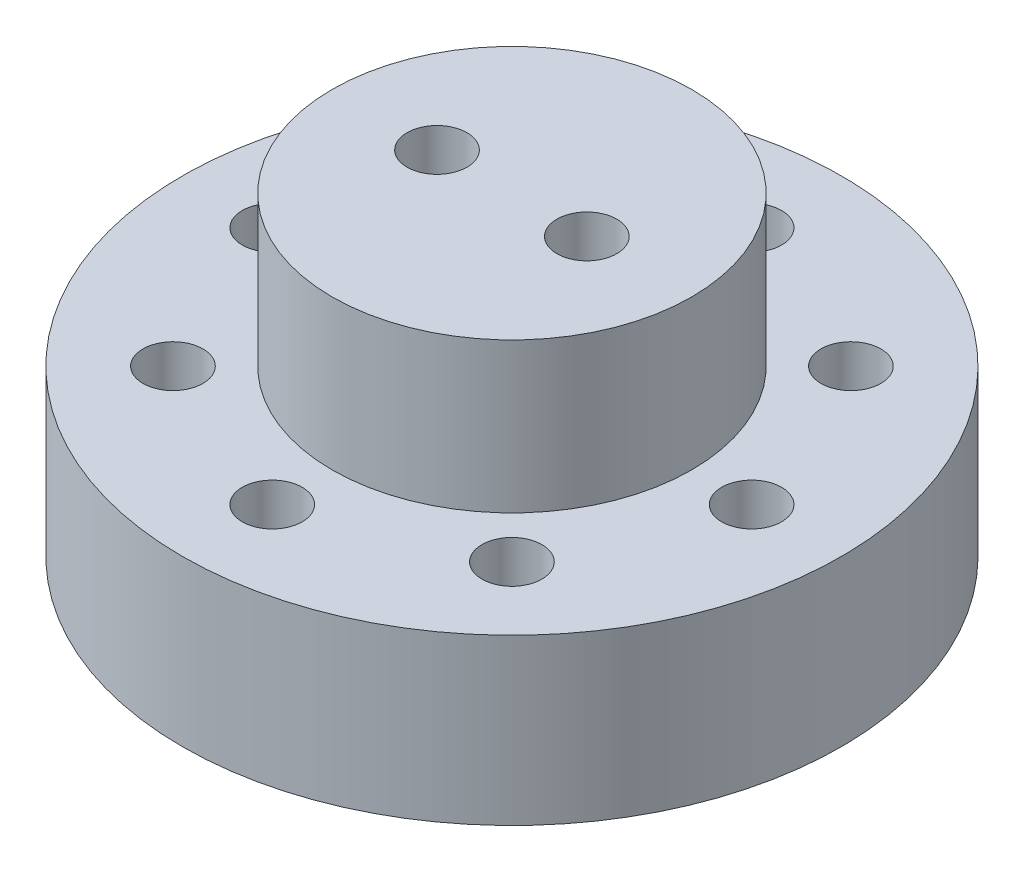
SolidWorks part; units mm, degrees
material "1060 Alloy"
ref_plane "Front Plane" through (0, 0, 0) normal (0, 0, 1) x (1, 0, 0)
ref_plane "Top Plane" through (0, 0, 0) normal (0, 1, 0) x (1, 0, 0)
ref_plane "Right Plane" through (0, 0, 0) normal (1, 0, 0) x (0, 0, -1)
sketch "Sketch1" plane through (0, 0, 0) normal (0, 1, 0) x (1, 0, 0)
  circle A0 centre (0, 0) radius 11
  circle A1 centre (0, 8) radius 1
  circle A2 centre (5.6569, 5.6569) radius 1
  circle A3 centre (8, 0) radius 1
  circle A4 centre (5.6569, -5.6569) radius 1
  circle A5 centre (0, -8) radius 1
  circle A6 centre (-5.6569, -5.6569) radius 1
  circle A7 centre (-8, 0) radius 1
  circle A8 centre (-5.6569, 5.6569) radius 1
  point P22 (0, 0)
  dimension "D1" = 22
  dimension "D2" = 2
  dimension "D6" = 8
  dimension "D3" = 8
  dimension "D5" = 8
  dimension "D4" = 8
extrude "Boss-Extrude1" add sketch "Sketch1" along normal blind 5.5
sketch "Sketch2" plane through (0, 5.5, 0) normal (0, 1, 0) x (1, 0, 0)
  circle A0 centre (0, 0) radius 4
  dimension "D1" = 8
extrude "Cut-Extrude1" cut sketch "Sketch2" against normal through all
ref_plane "Plane1" through (0, 3.5, 0) normal (0, 1, 0) x (1, 0, 0)
sketch "Sketch3" [suppressed] plane through (0, 3.5, 0) normal (0, 1, 0) x (1, 0, 0)
  circle A0 centre (0, 0) radius 5
  circle A1 centre (0, 0) radius 11
  dimension "D1" = 10
  dimension "D2" = 22
sketch "Sketch4" plane through (0, 5.5, 0) normal (0, 1, 0) x (1, 0, 0)
  line L1 (-0.75, 12.5) -> (0.75, 12.5)
  line L2 (-0.75, 12.5) -> (-0.75, 9.5)
  line L3 (-0.75, 9.5) -> (0.75, 9.5)
  line L4 (0.75, 12.5) -> (0.75, 9.5)
  line L5 (-0.75, 12.5) -> (0.75, 9.5) construction
  line L6 (-0.75, 9.5) -> (0.75, 12.5) construction
  circle A0 centre (0, 0) radius 11 construction
  point P0 (0, 11)
  dimension "D1" = 1.5
  dimension "D2" = 3
extrude "Cut-Extrude3" [suppressed] cut sketch "Sketch4" against normal blind 4
sketch "Sketch5" plane through (0, 5.5, 0) normal (0, 1, 0) x (1, 0, 0)
  circle A0 centre (0, 0) radius 4
  circle A1 centre (0, 0) radius 6
  dimension "D1" = 8
  dimension "D2" = 12
extrude "Boss-Extrude2" [suppressed] add sketch "Sketch5" along normal blind 20 contours A1 | A0
sketch "Sketch6" [suppressed] plane through (0, 22, 0) normal (0, 1, 0) x (1, 0, 0)
  line L0 (-0.255, 0.9669) -> (0.255, 0.9669)
  line L1 (-0.255, 0.9669) -> (-0.255, 1.4769)
  line L2 (0.255, 0.9669) -> (0.255, 1.4769)
  line L3 (-0.255, 1.4769) -> (0.255, 1.4769)
  line L4 (-0.254, -0.9672) -> (0.254, -0.9672)
  line L5 (-0.254, -0.9672) -> (-0.254, -1.4752)
  line L6 (0.254, -0.9672) -> (0.254, -1.4752)
  line L7 (-0.254, -1.4752) -> (0.254, -1.4752)
  line L8 (0.9672, 0.254) -> (0.9672, -0.254)
  line L9 (0.9672, 0.254) -> (1.4752, 0.254)
  line L10 (0.9672, -0.254) -> (1.4752, -0.254)
  line L11 (1.4752, 0.254) -> (1.4752, -0.254)
  line L12 (-0.9672, 0.254) -> (-0.9672, -0.254)
  line L13 (-0.9672, 0.254) -> (-1.4752, 0.254)
  line L14 (-0.9672, -0.254) -> (-1.4752, -0.254)
  line L15 (-1.4752, 0.254) -> (-1.4752, -0.254)
  circle A0 centre (0, 0) radius 1
  circle A1 centre (0, 0) radius 4
  circle A2 centre (0, 0) radius 6
  circle M4 centre (0, 0) radius 6
  circle M5 centre (0, 0) radius 4
  dimension "D1" = 2
  dimension "D4" = 8
  dimension "D5" = 12
  dimension "D2" = 0.51
  dimension "D3" = 0.51
  dimension "D6" = 0.508
  dimension "D7" = 0.508
  dimension "D8" = 0.508
  dimension "D9" = 0.508
  dimension "D10" = 0.508
  dimension "D11" = 0.508
extrude "Boss-Extrude3" [suppressed] add sketch "Sketch6" along normal blind 20 contours A0 L1 L3 L2 M5 | M4 M5
sketch "Sketch7" [suppressed] plane through (0, 0, 0) normal (0, 0, 1) x (1, 0, 0)
  line L0 (11, 3.5) -> (-11, 3.5) construction
  circle A0 centre (0, 38.5) radius 1
  dimension "D1" = 2
  dimension "D2" = 35
extrude "Cut-Extrude4" [suppressed] cut sketch "Sketch7" against normal blind 1 and the other way blind 5
sketch "Sketch9" plane through (0, 5.5, 0) normal (0, 1, 0) x (1, 0, 0)
  circle A0 centre (0, 0) radius 6
  dimension "D1" = 12
extrude "Boss-Extrude4" add sketch "Sketch9" along normal blind 5
sketch "Sketch10" plane through (0, 10.5, 0) normal (0, 1, 0) x (1, 0, 0)
  line L0 (-2.5, 0) -> (2.5, 0) construction
  circle A0 centre (-2.5, 0) radius 1
  circle A1 centre (2.5, 0) radius 1
  point P4 (0, 0)
  dimension "D2" = 2
  dimension "D3" = 2
  dimension "D1" = 5
extrude "Cut-Extrude6" cut sketch "Sketch10" against normal through all
ref_plane "Plane2" through (0, 0, 6) normal (0, 0, 1) x (1, 0, 0)
sketch "Sketch8" [suppressed] plane through (0, 0, 6) normal (0, 0, 1) x (1, 0, 0)
  circle A0 centre (0, 35) radius 2
  dimension "D1" = 4
extrude "Cut-Extrude5" [suppressed] cut sketch "Sketch8" against normal blind 1
